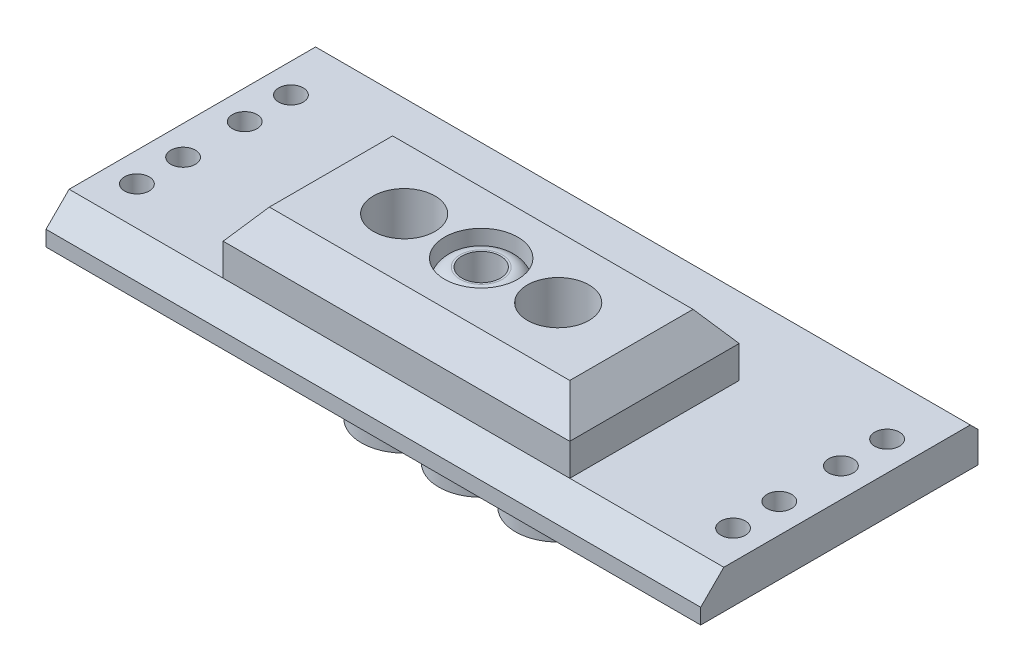
SolidWorks part; units mm, degrees
ref_plane "Alzado" through (0, 0, 0) normal (0, 0, 1) x (1, 0, 0)
ref_plane "Planta" through (0, 0, 0) normal (0, 1, 0) x (1, 0, 0)
ref_plane "Vista lateral" through (0, 0, 0) normal (1, 0, 0) x (0, 0, -1)
sketch "Croquis1" plane through (0, 0, 0) normal (0, 1, 0) x (1, 0, 0)
  line L0 (38.7, -5) -> (38.7, -11) construction
  line L1 (-42.5, -19) -> (42.5, -19)
  line L2 (-42.5, -19) -> (-42.5, 19)
  line L3 (-42.5, 19) -> (42.5, 19)
  line L4 (42.5, -19) -> (42.5, 19)
  line L5 (-42.5, -19) -> (42.5, 19) construction
  line L6 (-42.5, 19) -> (42.5, -19) construction
  line L7 (38.7, -11) -> (-38.7, -11) construction
  line L8 (-38.7, -5) -> (-38.7, -11) construction
  line L9 (38.7, 9) -> (38.7, 3) construction
  line L10 (38.7, 9) -> (38.7, 19) construction
  line L11 (38.7, 9) -> (42.5, 9) construction
  line L12 (-38.7, 9) -> (-38.7, 3) construction
  line L13 (-38.7, 9) -> (-38.7, 19) construction
  line L14 (0, 0) -> (0, -5) construction
  line L15 (-10, -5) -> (10, -5) construction
  circle A0 centre (38.7, -11) radius 1.6
  circle A1 centre (38.7, -5) radius 1.6
  circle A2 centre (-38.7, -11) radius 1.6
  circle A3 centre (-38.7, -5) radius 1.6
  circle A4 centre (38.7, 9) radius 1.6
  circle A5 centre (38.7, 3) radius 1.6
  circle A6 centre (-38.7, 3) radius 1.6
  circle A7 centre (-38.7, 9) radius 1.6
  circle A8 centre (0, -5) radius 2.5
  circle A9 centre (10, -5) radius 2.55
  circle A10 centre (-10, -5) radius 2.55
  point P0 (0, 0)
  point P31 (0, -5)
  dimension "D4" = 3.2
  dimension "D5" = 3.2
  dimension "D6" = 3.2
  dimension "D7" = 3.2
  dimension "D13" = 3.2
  dimension "D14" = 3.2
  dimension "D20" = 3.2
  dimension "D21" = 3.2
  dimension "D22" = 5
  dimension "D24" = 5.1
  dimension "D25" = 5.1
  dimension "D1" = 85
  dimension "D2" = 38
  dimension "D3" = 6
  dimension "D8" = 6
  dimension "D9" = 3.8
  dimension "D10" = 8
  dimension "D11" = 3.8
  dimension "D12" = 6
  dimension "D15" = 3.8
  dimension "D16" = 10
  dimension "D17" = 6
  dimension "D18" = 10
  dimension "D19" = 3.8
  dimension "D23" = 14
  dimension "D26" = 10
extrude "Saliente-Extruir1" add sketch "Croquis1" along normal blind 5
sketch "Croquis2" plane through (0, 5, 0) normal (0, 1, 0) x (1, 0, 0)
  line L0 (-42.5, -19) -> (42.5, -19) construction
  line L1 (0, -5) -> (0, 0) construction
  circle A0 centre (0, -5) radius 4.75
  circle A1 centre (0, -5) radius 2.5
  dimension "D2" = 9.5
  dimension "D3" = 5
  dimension "D1" = 14
extrude "Saliente-Extruir2" add sketch "Croquis2" along normal blind 7
fillet "Redondeo2" radius 2 1 edges at (0, 12, 9.75)
sketch "Croquis4" plane through (0, 5, 0) normal (0, 1, 0) x (1, 0, 0)
  line L0 (0, -5) -> (-10, -5) construction
  line L1 (0, -5) -> (10, -5) construction
  circle A0 centre (10, -5) radius 2.55
  circle A1 centre (-10, -5) radius 2.55
  circle A2 centre (-10, -5) radius 4
  circle A3 centre (10, -5) radius 4
  dimension "D1" = 5.1
  dimension "D2" = 5.1
  dimension "D5" = 8
  dimension "D6" = 8
  dimension "D3" = 10
  dimension "D4" = 10
extrude "Saliente-Extruir3" add sketch "Croquis4" along normal blind 3
fillet "Redondeo3" radius 2 2 edges at (-10, 8, 9) (10, 8, 9)
chamfer "Chaflán1" distance 3 angle 45 2 edges at (0, 5, -19) (0, 5, 19)
sketch "Croquis5" plane through (0, 5, 0) normal (0, 1, 0) x (1, 0, 0)
  line L1 (-22.5, 6) -> (22.5, 6)
  line L2 (-22.5, 6) -> (-22.5, -16)
  line L3 (-22.5, -16) -> (22.5, -16)
  line L4 (22.5, 6) -> (22.5, -16)
  line L5 (-22.5, 6) -> (22.5, -16) construction
  line L6 (-22.5, -16) -> (22.5, 6) construction
  line L7 (-16.5, 2) -> (16.5, 2)
  line L8 (-16.5, 2) -> (-16.5, -12)
  line L9 (-16.5, -12) -> (16.5, -12)
  line L10 (16.5, 2) -> (16.5, -12)
  line L11 (-16.5, 2) -> (16.5, -12) construction
  line L12 (-16.5, -12) -> (16.5, 2) construction
  point P0 (0, -5)
  point P6 (0, -5)
  circle M7 centre (-10, -5) radius 4
  circle M20 centre (0, -5) radius 4.75
  circle M21 centre (10, -5) radius 4
  dimension "D1" = 45
  dimension "D2" = 22
  dimension "D3" = 6
  dimension "D4" = 4
extrude "Saliente-Extruir4" add sketch "Croquis5" along normal blind 8 separate body contours L4 L1 L2 L3 L7 L10 L9 L8 | L8 L9 L7 M20 M7 | L10 L7 L9 M20 M21 region at (0, 5, -5.4991) region at (0, 5, -1.6415)
sketch "Croquis9" plane through (0, 0, 0) normal (0, -1, 0) x (1, 0, 0)
  line L0 (0, -55) -> (0, 55) construction
  circle A0 centre (0, 5) radius 5.5
  circle A1 centre (0, 5) radius 2.5 construction
  circle A2 centre (10, 5) radius 5.55
  circle A3 centre (10, 5) radius 2.55 construction
  circle A4 centre (-10, 5) radius 5.55
  circle M1 centre (10, 5) radius 2.55
  circle M14 centre (0, 5) radius 2.5
  circle M15 centre (-10, 5) radius 2.55
  dimension "D1" = 3
  dimension "D2" = 3
extrude "Saliente-Extruir7" add sketch "Croquis9" along normal blind 10 contours A0 A2 M1 | A0 A4 A2 M14 | A4 A0 M15 | A0 A2 | A4 A0 region at (4.9745, 0, 5) region at (5.5161, 0, 6.2381) region at (4.3017, 0, 5) region at (-4.9745, 0, 5) region at (-5.6533, 0, 5)
chamfer "Chaflán2" distance 3 angle 52 4 edges at (22.5, 13, 5) (-22.5, 13, 5) (0, 13, -6) (0, 13, 16) first distance on face at (0, 13, 5)
sketch "Croquis10" plane through (0, 0, 0) normal (0, -1, 0) x (1, 0, 0)
  line L0 (42.5, 19) -> (42.5, -19) construction
  line L1 (-42.5, -17) -> (42.5, -17)
  line L2 (-42.5, -17) -> (-42.5, -19)
  line L3 (-42.5, -19) -> (42.5, -19)
  line L4 (42.5, -17) -> (42.5, -19)
extrude "Cortar-Extruir1" cut sketch "Croquis10" against normal through all
